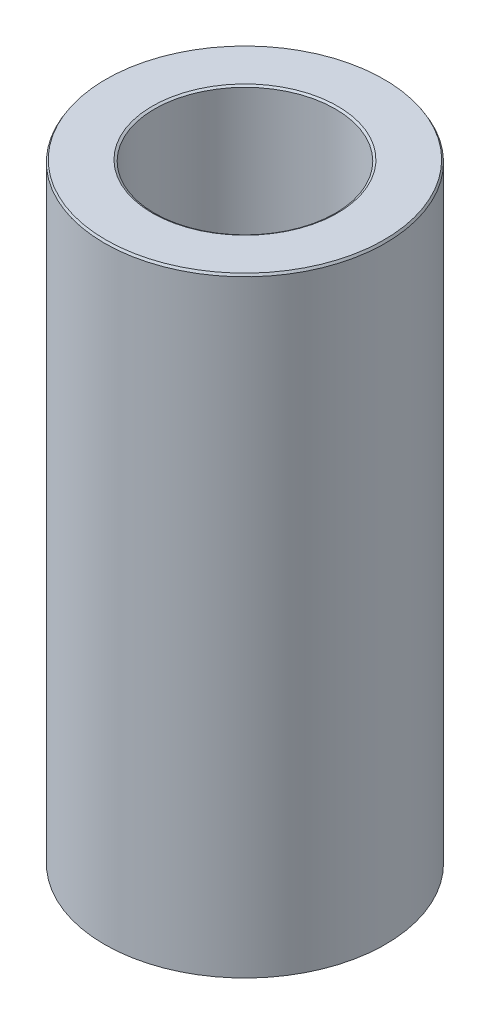
SolidWorks part; units mm, degrees
ref_plane "Front Plane" through (0, 0, 0) normal (0, 0, 1) x (1, 0, 0)
ref_plane "Top Plane" through (0, 0, 0) normal (0, 1, 0) x (1, 0, 0)
ref_plane "Right Plane" through (0, 0, 0) normal (1, 0, 0) x (0, 0, -1)
sketch "Sketch1" plane through (0, 0, 0) normal (0, 1, 0) x (1, 0, 0)
  circle A0 centre (0, 0) radius 42.5
  dimension "SLEEVE_OD" = 85
extrude "Boss-Extrude1" add sketch "Sketch1" along normal blind 184.8621
sketch "Sketch2" plane through (0, 0, 0) normal (0, 1, 0) x (1, 0, 0)
  circle A0 centre (0, 0) radius 27.3587
  dimension "BORE_D" = 54.7175
extrude "Cut-Extrude1" cut sketch "Sketch2" along normal through all
chamfer "Chamfer1" distance 0.6762 angle 30.89 4 edges at (0, 184.8621, 27.3587) (0, 0, 27.3587) (0, 0, 42.5) (0, 184.8621, 42.5) first distance on face at (0, 184.8621, 27.3587) first distance on face at (0, 0, 27.3587) first distance on face at (0, 184.8621, 42.5)
